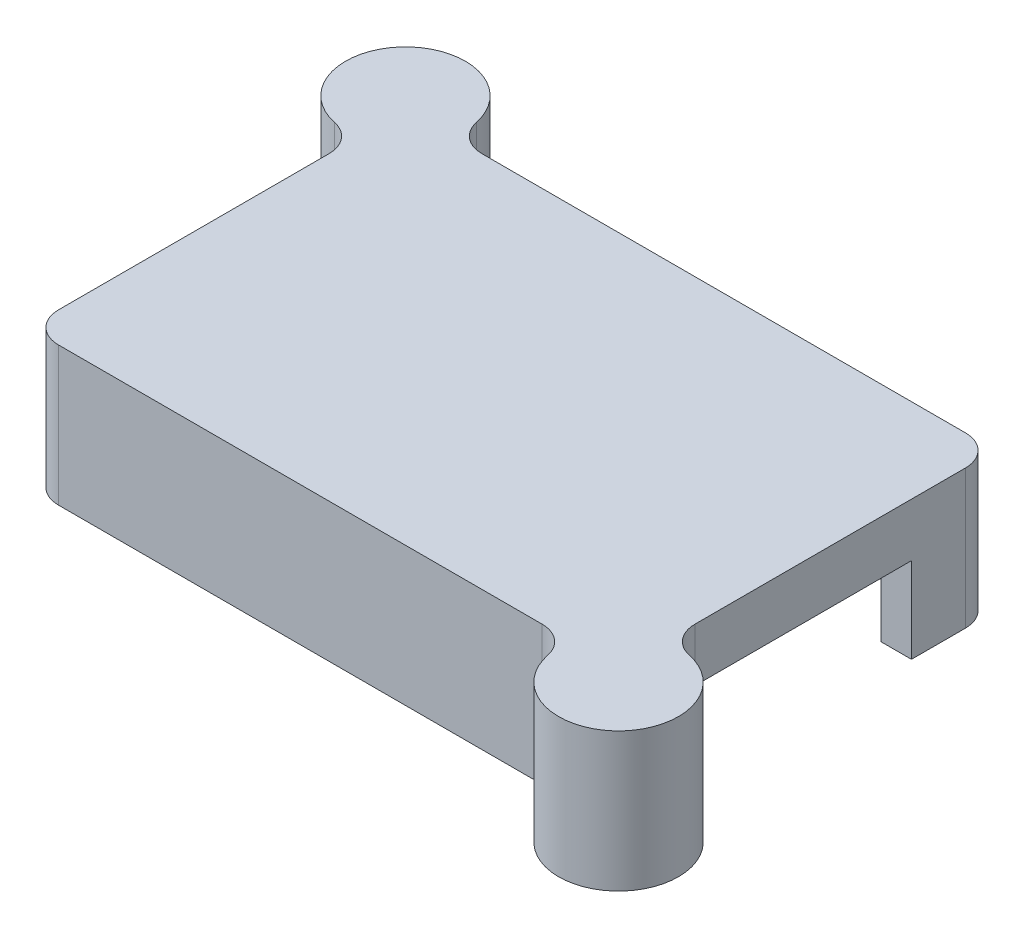
SolidWorks part; units mm, degrees
ref_plane "Front Plane" through (0, 0, 0) normal (0, 0, 1) x (1, 0, 0)
ref_plane "Top Plane" through (0, 0, 0) normal (0, 1, 0) x (1, 0, 0)
ref_plane "Right Plane" through (0, 0, 0) normal (1, 0, 0) x (0, 0, -1)
sketch "Sketch2" plane through (-16.2488, 1.905, 5.926) normal (0, 1, 0) x (1, 0, 0)
  line L0 (-20.8597, -11.957) -> (-20.8597, 11.9571) construction
  line L1 (22.1298, -13.227) -> (-22.1298, -13.227)
  line L2 (22.1298, -13.227) -> (22.1298, 13.2271)
  line L3 (22.1298, 13.2271) -> (-22.1298, 13.2271)
  line L4 (-22.1298, -13.227) -> (-22.1298, 13.2271)
  line L5 (22.1298, -13.227) -> (-22.1298, 13.2271) construction
  line L6 (22.1298, 13.2271) -> (-22.1298, -13.227) construction
  line L7 (-20.8597, 11.9571) -> (20.8597, 11.957) construction
  line L8 (24.6698, -15.767) -> (24.6698, 15.7671)
  line L9 (24.6698, 15.7671) -> (-24.6698, 15.767)
  line L10 (-24.6698, -15.767) -> (-24.6698, 15.767)
  line L11 (24.6698, -15.767) -> (-24.6698, -15.767)
  point P0 (0, 0)
  dimension "D1" = 1.27
  dimension "D2" = 1.27
  dimension "D3" = 2.54
extrude "Boss-Extrude1" add sketch "Sketch2" along normal blind 1.905 contours L4 L1 L2 L3 | L11 L8 L9 L10 L1 L4 L3 L2 region at (-16.2488, 1.905, 5.926) region at (-16.2488, 1.905, 21.1075)
extrude "Boss-Extrude2" add sketch "Sketch2<3>" against normal offset from surface (9.6901 mm away) 1.27 offset beyond the face yes
sketch "Sketch2<3>" plane through (-16.2488, 1.905, 5.926) normal (0, 1, 0) x (1, 0, 0) same geometry as "Sketch2"
sketch "Sketch4" plane through (0, -7.7851, 0) normal (0, -1, 0) x (1, 0, 0)
  line L0 (5.8809, 19.153) -> (8.4209, 21.693) construction
  line L1 (8.4209, 21.693) -> (9.4191, 22.6913) construction
  line L2 (-16.2488, 21.693) -> (-16.2488, 31.4228) construction
  line L3 (8.4209, 21.693) -> (-40.9186, 21.693) construction
  line L4 (-40.9186, 5.926) -> (-49.1029, 5.926) construction
  line L5 (-40.9186, 21.693) -> (-40.9186, -9.8411) construction
  circle A0 centre (9.4191, 22.6913) radius 5.0038
  circle A1 centre (9.4191, 22.6913) radius 2.413
  circle A2 centre (-41.9168, 22.6913) radius 2.413 construction
  circle A3 centre (-41.9168, 22.6913) radius 5.0038 construction
  circle A4 centre (-41.9168, -10.8393) radius 2.413
  circle A5 centre (-41.9168, -10.8393) radius 5.0038
  line M3 (8.4209, 21.693) -> (-40.9186, 21.693)
  line M4 (-40.9186, 21.693) -> (-40.9186, -9.8411)
  line M5 (-40.9186, -9.8411) -> (8.4209, -9.8411)
  line M6 (8.4209, -9.8411) -> (8.4209, 21.693)
  dimension "D1" = 10.0076
  dimension "D2" = 4.826
extrude "Boss-Extrude4" add sketch "Sketch4" against normal up to surface (11.5951 mm away) contours A4 M4 M5 | A5 A4 M4 M5 | A1 M6 M3 | A1 A0 M6 M3 region at (12.4953, -7.7851, 18.9258) region at (9.4933, -7.7851, 22.7655) region at (-41.0601, -7.7851, -7.2892) region at (-41.991, -7.7851, -10.9135) up to face at (-16.2488, 3.81, 5.926)
extrude "Cut-Extrude1" cut sketch "Sketch4<3>" against normal blind 6.35 contours A4 M4 M5 | A1 M6 M3 | A1 M3 M6 | A4 M5 M4 region at (7.9737, -7.7851, 21.2459) region at (9.4933, -7.7851, 22.7655) region at (-41.991, -7.7851, -10.9135) region at (-40.4714, -7.7851, -9.3939)
sketch "Sketch4<3>" plane through (0, -7.7851, 0) normal (0, -1, 0) x (1, 0, 0) same geometry as "Sketch4"
sketch "Sketch6" plane through (0, -1.4351, 0) normal (0, -1, 0) x (1, 0, 0)
  circle A0 centre (9.4191, 22.6913) radius 1.5
  circle A1 centre (-41.9168, -10.8393) radius 1.5
  dimension "D1" = 3
extrude "Cut-Extrude2" cut sketch "Sketch6" against normal blind 3.429
ref_plane "Plane1" through (9.4191, 0, 0) normal (-1, 0, 0) x (0, -1, 0)
ref_plane "Plane2" through (0, 0, -10.8393) normal (0, 0, -1) x (0, -1, 0)
sketch "Sketch7" plane through (0, 0, -10.8393) normal (0, 0, -1) x (0, -1, 0)
  line L0 (1.4351, 43.5971) -> (7.7851, 44.7168)
  line L1 (7.7851, 44.7168) -> (7.7851, 41.9168)
  line L2 (7.7851, 41.9168) -> (1.4351, 41.9168)
  line L3 (1.4351, 41.9168) -> (1.4351, 43.5971)
  line L4 (7.7851, -11.8321) -> (7.7851, -7.0061) construction
  line L5 (-3.81, 41.9168) -> (7.7851, 41.9168) construction
  dimension "D1" = 2.8
  dimension "D2" = 1.6803
revolve "Cut-Revolve1" cut sketch "Sketch7" angle 360 about L2
sketch "Sketch8" plane through (9.4191, 0, 0) normal (-1, 0, 0) x (0, -1, 0)
  line L0 (1.4351, 24.3716) -> (7.7851, 25.4913)
  line L1 (7.7851, 25.4913) -> (7.7851, 22.6913)
  line L2 (7.7851, 22.6913) -> (1.4351, 22.6913)
  line L3 (1.4351, 22.6913) -> (1.4351, 24.3716)
  line L4 (7.7851, -13.6393) -> (7.7851, -8.0393) construction
  line L7 (-3.81, 22.6913) -> (7.7851, 22.6913) construction
  dimension "D1" = 2.8
  dimension "D2" = 1.6803
revolve "Cut-Revolve2" cut sketch "Sketch8" angle 360 about L2
sketch "Sketch9" plane through (0, 1.905, 0) normal (0, -1, 0) x (1, 0, 0)
  circle A0 centre (-35.1086, 15.883) radius 1
  circle A1 centre (2.6109, -4.0311) radius 1
extrude "Boss-Extrude6" add sketch "Sketch9" along normal blind 2.794 draft 2
sketch "Sketch10" plane through (8.4209, 0, 0) normal (1, 0, 0) x (0, 0, -1)
  line L1 (-14.6382, -0.6425) -> (2.7862, -0.6425)
  line L2 (-14.6382, -0.6425) -> (-14.6382, -7.7851)
  line L3 (-14.6382, -7.7851) -> (2.7862, -7.7851)
  line L4 (2.7862, -0.6425) -> (2.7862, -7.7851)
  line L5 (1.5162, -6.5151) -> (1.5162, -5.2451) construction
  line L6 (-13.3682, -6.5151) -> (-13.3682, -5.2451) construction
  line L8 (-19.153, -7.7851) -> (7.3011, -7.7851) construction
  dimension "D1" = 1.27
  dimension "D2" = 1.27
  dimension "D3" = 7.1426
extrude "Cut-Extrude3" cut sketch "Sketch10" against normal up to surface (2.54 mm away) up to face at (5.8809, -2.9401, 5.926)
sketch "Sketch11" plane through (-40.9186, 0, 0) normal (-1, 0, 0) x (0, 0, 1)
  line L0 (13.7365, -6.5151) -> (13.7365, -5.2451) construction
  line L1 (-3.1545, -0.6425) -> (15.0065, -0.6425)
  line L2 (-3.1545, -0.6425) -> (-3.1545, -7.7851)
  line L3 (-3.1545, -7.7851) -> (15.0065, -7.7851)
  line L4 (15.0065, -0.6425) -> (15.0065, -7.7851)
  line L5 (-1.8845, -6.5151) -> (-1.8845, -5.2451) construction
  line L6 (-7.3011, -7.7851) -> (-2.7862, -7.7851) construction
  line L7 (14.6382, -0.6425) -> (-2.7862, -0.6425) construction
  dimension "D1" = 1.27
  dimension "D2" = 1.27
extrude "Cut-Extrude4" cut sketch "Sketch11" against normal up to surface (2.54 mm away) up to face at (-38.3786, -2.9401, 5.926)
fillet "Fillet1" radius 2.54 2 edges at (8.4209, -1.9876, -9.8411) (-40.9186, -1.9876, 21.693)
fillet "Fillet2" radius 1.27 4 edges at (-38.3786, -2.9401, -7.3011) (5.8809, -2.9401, -7.3011) (5.8809, -2.9401, 19.153) (-38.3786, -2.9401, 19.153)
sketch "Sketch12" plane through (0, -7.7851, 0) normal (0, -1, 0) x (1, 0, 0)
  line L0 (4.5159, 21.693) -> (-38.3786, 21.693) construction
  line L1 (-16.0541, 21.693) -> (-18.7633, 21.693) construction
  line L2 (9.3457, 37.4487) -> (9.8226, 38.7929) construction
  line L3 (1.2824, 21.693) -> (4.5159, 21.693)
  line L4 (8.4209, 14.6382) -> (8.4209, 17.788) construction
  line L6 (8.4209, 20.0754) -> (8.4209, 22.3072) construction
  line L7 (-10.5305, -0.1527) -> (-11.9859, -1.347) construction
  line L8 (8.4209, 14.6382) -> (8.4209, 17.788)
  line L9 (-15.5663, -9.8411) -> (-15.5663, -12.7104) construction
  line L10 (-37.0136, -9.8411) -> (5.8809, -9.8411) construction
  line L11 (8.4209, 5.926) -> (15.0851, 5.926) construction
  line L12 (8.4209, -2.7862) -> (8.4209, 14.6382) construction
  line L13 (12.5934, 18.8232) -> (10.211, 18.8232) construction
  line L14 (4.2738, 11.996) -> (20.9129, 25.6503) construction
  arc A0 (8.4209, 17.788) -> (4.5159, 21.693) centre (9.4191, 22.6913) ccw construction
  arc A1 (4.7034, 24.3644) -> (4.5159, 21.693) centre (9.4191, 22.6913) ccw
  arc A3 (8.4209, 17.788) -> (12.5934, 18.8232) centre (9.4191, 22.6913) ccw
  arc A4 (4.7034, 24.3644) -> (4.5159, 21.693) centre (9.4191, 22.6913) ccw
  spline S0 degree 3 poles (4.7034, 24.3644) (4.4053, 23.5243) (2.9757, 21.693) (1.2824, 21.693) knots 0 0 0 0 1 1 1 1
  spline S1 degree 3 poles (12.5934, 18.8232) (9.8202, 16.5474) (8.4209, 16.3255) (8.4209, 14.6382) knots 0 0 0 0 1 1 1 1
  point P30 (0, 0)
  dimension "D2" = 39.373
  dimension "D3" = 10.7622
  dimension "D4" = 5.0619
  dimension "D1" = 3.2335
  dimension "D5" = 2.3824
  dimension "D6" = 3.1499
fillet "Fillet3" radius 2.54 4 edges at (-37.0136, -1.9876, -9.8411) (-40.9186, -1.9876, -5.9361) (8.4209, -1.9876, 17.788) (4.5159, -1.9876, 21.693)
